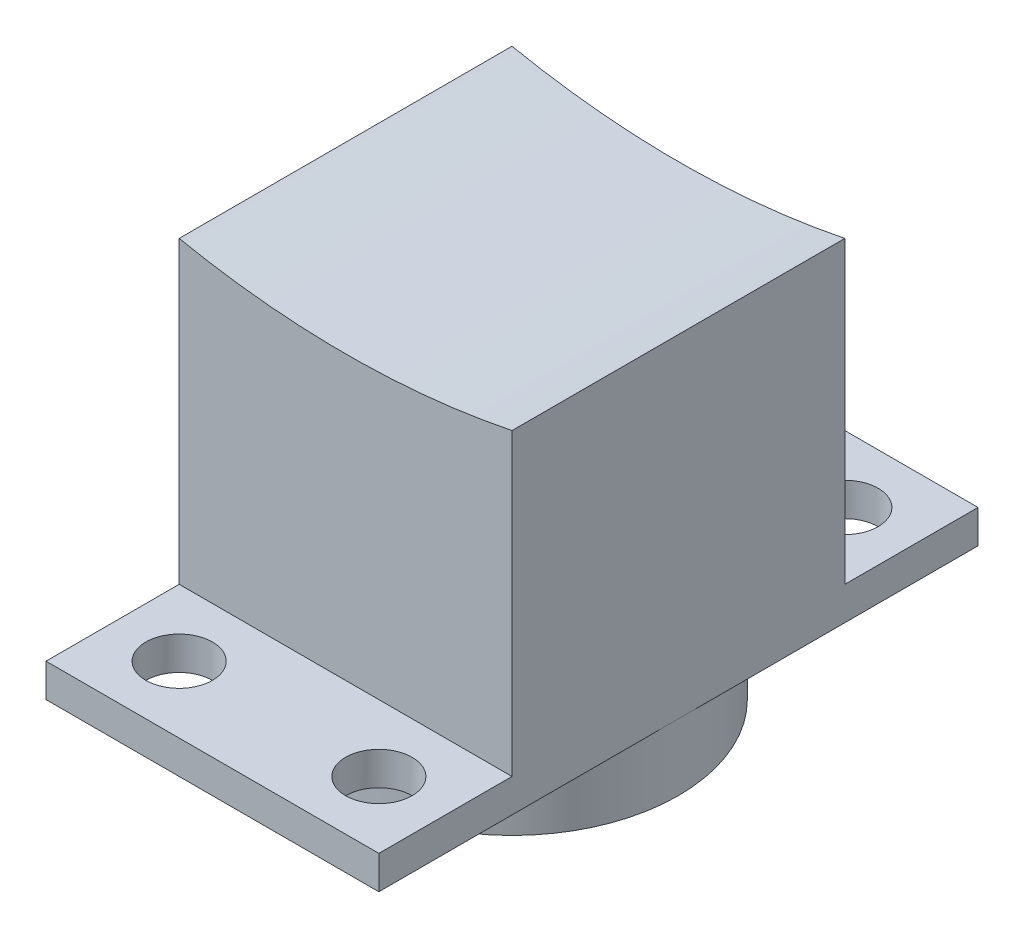
SolidWorks part; units mm, degrees
ref_plane "Front Plane" through (0, 0, 0) normal (0, 0, 1) x (1, 0, 0)
ref_plane "Top Plane" through (0, 0, 0) normal (0, 1, 0) x (1, 0, 0)
ref_plane "Right Plane" through (0, 0, 0) normal (1, 0, 0) x (0, 0, -1)
sketch "Sketch1" plane through (0, 0, 0) normal (0, 0, 1) x (1, 0, 0)
  line L2 (25, 25) -> (25, -25)
  line L3 (25, -25) -> (-25, -25)
  line L4 (-25, 25) -> (-25, -25)
  arc A0 (-25, 25) -> (25, 25) centre (0, 147.4684) ccw
  point P0 (0, 0)
  dimension "D5" = 249.988
  dimension "D1" = 50
  dimension "D2" = 50
  dimension "D3" = 25
  dimension "D4" = 50
extrude "Boss-Extrude1" add sketch "Sketch1" along normal blind 50
sketch "Sketch2" plane through (0, -25, 0) normal (0, -1, 0) x (1, 0, 0)
  circle A0 centre (0, 25) radius 25
  dimension "D1" = 25
extrude "Boss-Extrude2" add sketch "Sketch2" along normal blind 10
sketch "Sketch3" plane through (0, 0, 50) normal (0, 0, 1) x (1, 0, 0)
  line L0 (25, -25) -> (25, 25) construction
  line L1 (-25, -25) -> (25, -25)
  line L2 (-25, -25) -> (-25, -20)
  line L3 (-25, -20) -> (25, -20)
  line L4 (25, -25) -> (25, -20)
  dimension "D1" = 5
extrude "Boss-Extrude3" add sketch "Sketch3" along normal blind 20 and the other way blind 70
sketch "Sketch4" plane through (0, -20, 0) normal (0, 1, 0) x (1, 0, 0)
  line L0 (25, -70) -> (-25, -70) construction
  line L1 (-25, -50) -> (-25, -70) construction
  line L2 (25, -50) -> (25, -70) construction
  line L4 (25, 20) -> (-25, 20) construction
  circle A0 centre (-15, -60) radius 5
  circle A1 centre (15, -60) radius 5
  circle A2 centre (15, 10) radius 5
  circle A3 centre (-15, 10) radius 5
  dimension "D1" = 10
  dimension "D2" = 10
  dimension "D7" = 10
  dimension "D8" = 10
  dimension "D3" = 10
  dimension "D4" = 10
  dimension "D5" = 10
  dimension "D6" = 10
  dimension "D9" = 10
  dimension "D10" = 10
extrude "Cut-Extrude1" cut sketch "Sketch4" against normal blind 10
equation "\"ThrusterDim\"= 140mm"
equation "\"hatchHoleDiameter\"= 600mm"
equation "\"hullThickness\"= 120mm"
equation "\"gasketHullInterconnectWidth\"= 100mm"
equation "\"collarThickness\"= 15"
equation "\"hatchTunnelLength\"=200"
equation "\"oRingDiameter\"=2"
equation "\"boltPatternRadiusInterconnect\"=500"
equation "\"interconnectBoltDiameter\"=30"
equation "\"hatchShaftDiameter\"=20"
equation "\"hatchMinima\"=50"
equation "\"hullDiameter\"=2000"
equation "\"hatchMaxima\"=180"
equation "\"bushingFlatHatch\"=15"
equation "\"hingePivotDiameter\"=20"
equation "\"handleWidth\"=250"
equation "\"handleHeight\"=160"
equation "\"handleThickness\"=25"
equation "\"FrameLength\"= 4300"
equation "\"FrameMidLength\"= 3000"
equation "\"TubeOD\"= 100"
equation "\"FrameBackFlat\"= 800"
equation "\"TubeWall\"=15"
equation "\"TopMemberAngle\"=120"
equation "\"FrameHight\"= 2500"
equation "\"D5@Sketch1\"=\"ThrusterDim\" *2 *0.8571+10"
